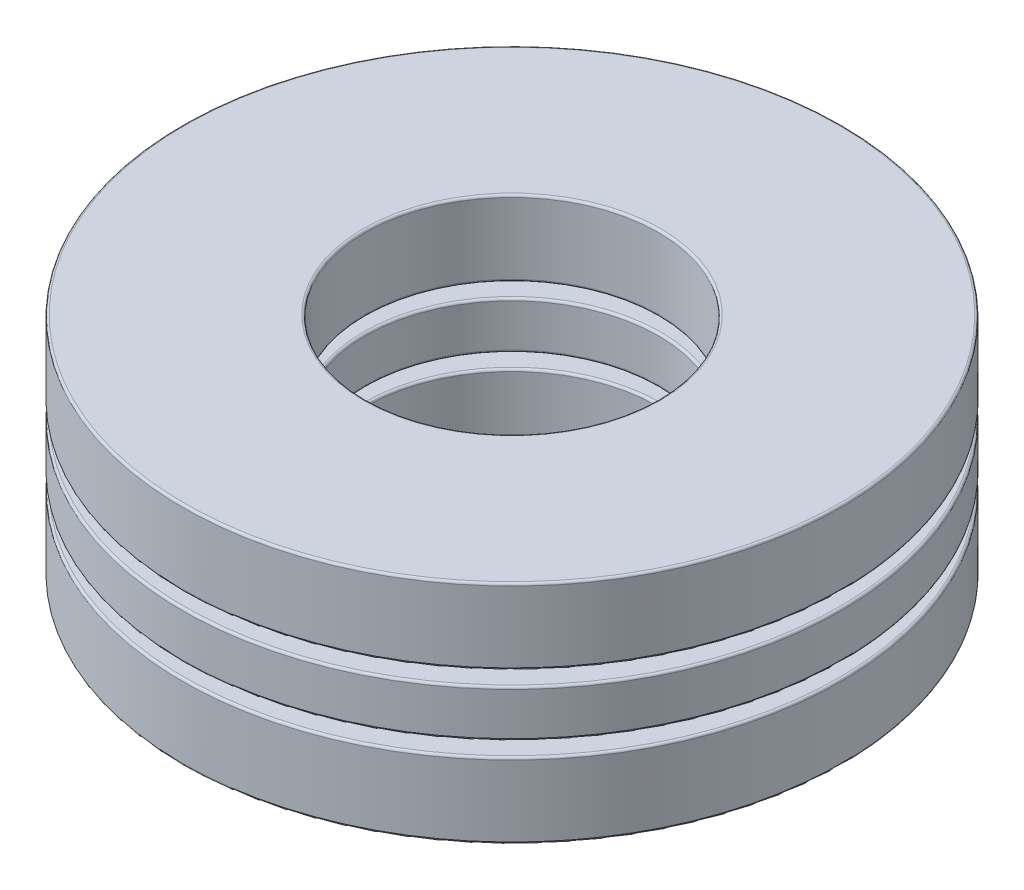
SolidWorks part; units mm, degrees
ref_plane "Front Plane" through (0, 0, 0) normal (0, 0, 1) x (1, 0, 0)
ref_plane "Top Plane" through (0, 0, 0) normal (0, 1, 0) x (1, 0, 0)
ref_plane "Right Plane" through (0, 0, 0) normal (1, 0, 0) x (0, 0, -1)
sketch "Sketch1" plane through (0, 0, 0) normal (1, 0, 0) x (0, 0, -1)
  line L0 (-7.1438, 0) -> (7.1438, 0) construction
  line L1 (0, -2.4511) -> (0, 2.4511) construction
  line L2 (-7.1438, 0.5106) -> (-3.175, 0.5106)
  line L3 (-7.1438, 0.5106) -> (-7.1438, -0.5106)
  line L4 (-7.1438, -0.5106) -> (-3.175, -0.5106)
  line L5 (-3.175, 0.5106) -> (-3.175, -0.5106)
  line L6 (-5.1594, 0.817) -> (-5.1594, -0.817) construction
  circle A0 centre (-5.1594, 0) radius 0.817 construction
  point P13 (-5.1594, 0.5106)
  dimension "D1" = 1.6341
  dimension "OD" = 14.2875
  dimension "Shaft Dia" = 6.35
  dimension "Th" = 4.9022
  dimension "D2" = 1.0213
revolve "Revolve1" add sketch "Sketch1" angle 360 about L1
sketch "Sketch3" plane through (0, 0, 0) normal (1, 0, 0) x (0, 0, -1)
  line L0 (-5.1594, 0.817) -> (-5.1594, -0.817)
  arc A0 (-5.1594, 0.817) -> (-5.1594, -0.817) centre (-5.1594, 0) ccw
  circle A1 centre (-5.1594, 0) radius 0.817 construction
revolve "Cut-Revolve1" cut sketch "Sketch3" angle 360 about L0
sketch "Sketch2" plane through (0, 0, 0) normal (1, 0, 0) x (0, 0, -1)
  line L0 (-5.1594, 0.817) -> (-5.1594, -0.817)
  arc A0 (-5.1594, 0.817) -> (-5.1594, -0.817) centre (-5.1594, 0) ccw
  circle A2 centre (-5.1594, 0) radius 0.817 construction
revolve "Revolve2" add sketch "Sketch2" angle 360 about L0
ref_axis "Axis1" through (0, 2.4511, 0) along (0, -1, 0)
pattern_circular "CirPattern1" count 7 every 51.429 about axis through (0, 2.4511, 0) along (0, -1, 0) of bodies 187
pattern_circular "CirPattern2" count 7 every 51.429 about axis through (0, 2.4511, 0) along (0, -1, 0) of "Cut-Revolve1"
sketch "Sketch4" plane through (0, 0, 0) normal (1, 0, 0) x (0, 0, -1)
  line L0 (-7.1438, 0.5106) -> (-7.1438, -0.5106) construction
  line L1 (-7.1438, 0.817) -> (-3.175, 0.817)
  line L2 (-7.1438, 0.817) -> (-7.1438, 2.4511)
  line L3 (-7.1438, 2.4511) -> (-3.175, 2.4511)
  line L4 (-3.175, 0.817) -> (-3.175, 2.4511)
  line L5 (-7.1438, -2.4511) -> (-3.175, -2.4511)
  line L6 (-7.1438, -2.4511) -> (-7.1438, -0.817)
  line L7 (-7.1438, -0.817) -> (-3.175, -0.817)
  line L8 (-3.175, -2.4511) -> (-3.175, -0.817)
  line L9 (-5.1594, 0.817) -> (-5.1594, -0.817) construction
  line L10 (-3.175, 0.5106) -> (-3.175, -0.5106) construction
  line L11 (0, 0) -> (-7.1438, 0) construction
  line L12 (-7.1438, 0) -> (7.1438, 0) construction
  dimension "Ht" = 4.9022
revolve "Revolve3" add sketch "Sketch4" angle 360 about L1
fillet "Fillet1" radius 0.049 4 edges at (0, 0.817, -3.175) (0, 2.4511, -3.175) (0, 0.817, -7.1438) (0, 2.4511, -7.1438)
fillet "Fillet2" radius 0.049 4 edges at (0, -0.5106, -3.175) (0, 0.5106, -3.175) (0, -0.5106, -7.1438) (0, 0.5106, -7.1438)
fillet "Fillet3" radius 0.049 4 edges at (0, -2.4511, -3.175) (0, -0.817, -3.175) (0, -2.4511, -7.1438) (0, -0.817, -7.1438)
equation "\"D1@Sketch1\" = \"Th@Sketch1\"/3"
equation "\"D2@Sketch1\" = \"D1@Sketch1\"*.625"
equation "\"Balls@CirPattern1\" = \"OD@Sketch1\"*12"
equation "\"Angle@CirPattern1\" = 360/\"Balls@CirPattern1\""
equation "\"D1@CirPattern2\" = \"Balls@CirPattern1\""
equation "\"D2@CirPattern2\" = \"Angle@CirPattern1\""
equation "\"D1@Fillet1\" = \"Th@Sketch1\"*.01"
equation "\"D1@Fillet2\" = \"D1@Fillet1\""
equation "\"D1@Fillet3\" = \"D1@Fillet1\""
